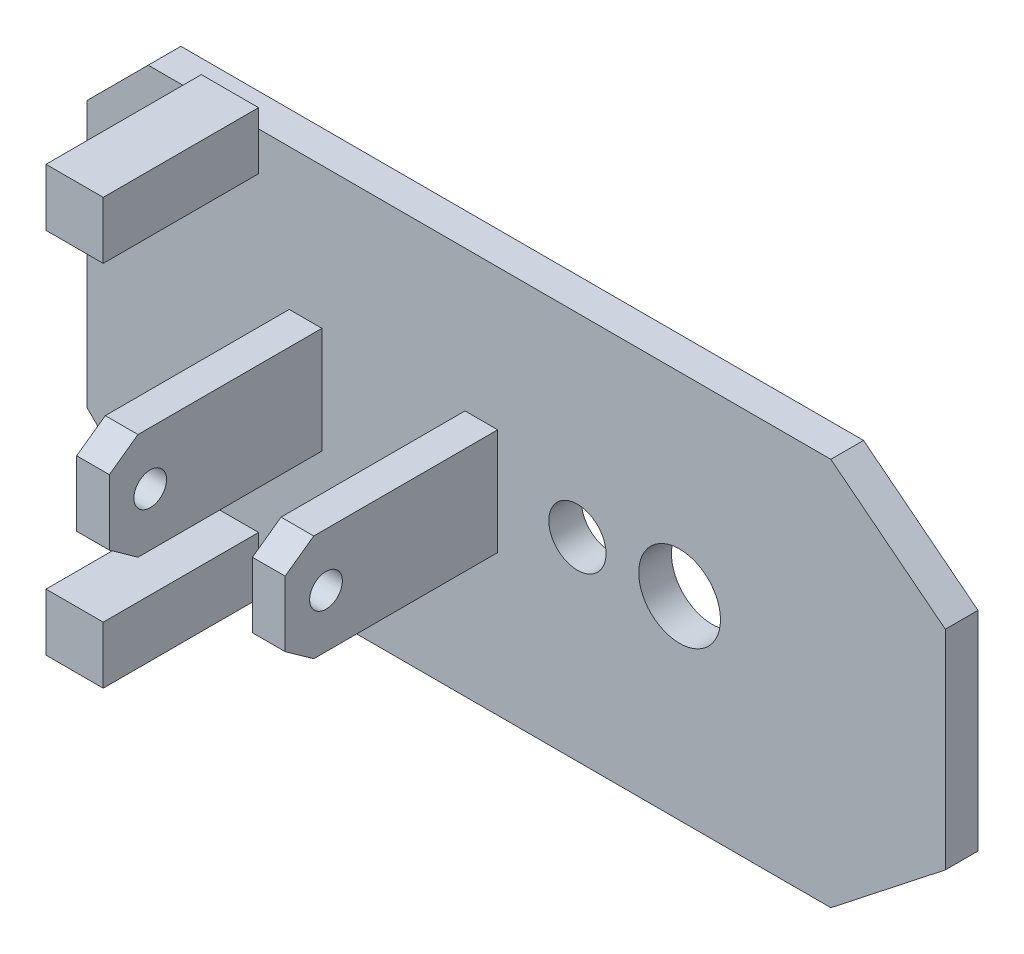
SolidWorks part; units mm, degrees
material "6061-T6 (SS)"
ref_plane "Front Plane" through (0, 0, 0) normal (0, 0, 1) x (1, 0, 0)
ref_plane "Top Plane" through (0, 0, 0) normal (0, 1, 0) x (1, 0, 0)
ref_plane "Right Plane" through (0, 0, 0) normal (1, 0, 0) x (0, 0, -1)
ref_plane "PL_Sole_Plate_base" through (0, 0, -50) normal (0, 0, 1) x (1, 0, 0)
sketch "SK_Sole_Plate" plane through (0, 0, -50) normal (0, 0, 1) x (1, 0, 0)
  line L0 (-60, -47.5) -> (107, -47.5)
  line L1 (107, -47.5) -> (135, -25.5)
  line L2 (135, -25.5) -> (135, 25.5)
  line L3 (135, 25.5) -> (107, 47.5)
  line L4 (107, 47.5) -> (-60, 47.5)
  line L5 (-60, 47.5) -> (-75, 32.5)
  line L6 (-75, 32.5) -> (-75, -32.5)
  line L7 (-75, -32.5) -> (-60, -47.5)
  circle A0 centre (70, 0) radius 10
  circle A1 centre (45, 0) radius 7
  dimension "D17_SK_Sole_Plate" = 20
  dimension "D19_SK_Sole_Plate" = 14
  dimension "P1" = 60
  dimension "P2" = 47.5
  dimension "P3" = 107
  dimension "P4" = 47.5
  dimension "P5" = 135
  dimension "P6" = 25.5
  dimension "P7" = 135
  dimension "P8" = 25.5
  dimension "P9" = 107
  dimension "P10" = 47.5
  dimension "P11" = 60
  dimension "P12" = 47.5
  dimension "P13" = 75
  dimension "P14" = 32.5
  dimension "P15" = 75
  dimension "P16" = 32.5
  dimension "P18" = 70
  dimension "P20" = 45
extrude "Sole_Plate" add sketch "SK_Sole_Plate" along normal blind 8
ref_plane "PL_Clevis_Front_base" through (17.5, 0, 0) normal (1, 0, 0) x (0, 0, -1)
sketch "SK_Clevis_Front" plane through (17.5, 0, 0) normal (1, 0, 0) x (0, 0, -1)
  line L0 (42, -13) -> (42, 13)
  line L1 (42, 13) -> (-3, 13)
  line L2 (-3, 13) -> (-10, 8)
  line L3 (-10, 8) -> (-10, -8)
  line L4 (-10, -8) -> (-3, -13)
  line L5 (-3, -13) -> (42, -13)
  circle A0 centre (0, 0) radius 4
  dimension "D13_SK_Clevis_Front" = 8
  dimension "P1" = 42
  dimension "P2" = 13
  dimension "P3" = 42
  dimension "P4" = 13
  dimension "P5" = 3
  dimension "P6" = 13
  dimension "P7" = 10
  dimension "P8" = 8
  dimension "P9" = 10
  dimension "P10" = 8
  dimension "P11" = 3
  dimension "P12" = 13
extrude "Clevis_Front" add sketch "SK_Clevis_Front" along normal blind 8
ref_plane "PL_Clevis_Back_base" through (-25.5, 0, 0) normal (1, 0, 0) x (0, 0, -1)
sketch "SK_Clevis_Back" plane through (-25.5, 0, 0) normal (1, 0, 0) x (0, 0, -1)
  line L0 (42, -13) -> (42, 13)
  line L1 (42, 13) -> (-3, 13)
  line L2 (-3, 13) -> (-10, 8)
  line L3 (-10, 8) -> (-10, -8)
  line L4 (-10, -8) -> (-3, -13)
  line L5 (-3, -13) -> (42, -13)
  circle A0 centre (0, 0) radius 4
  dimension "D13_SK_Clevis_Back" = 8
  dimension "P1" = 42
  dimension "P2" = 13
  dimension "P3" = 42
  dimension "P4" = 13
  dimension "P5" = 3
  dimension "P6" = 13
  dimension "P7" = 10
  dimension "P8" = 8
  dimension "P9" = 10
  dimension "P10" = 8
  dimension "P11" = 3
  dimension "P12" = 13
extrude "Clevis_Back" add sketch "SK_Clevis_Back" along normal blind 8
ref_plane "PL_Post_Lat_base" through (0, 0, -42) normal (0, 0, 1) x (1, 0, 0)
sketch "SK_Post_Lat" plane through (0, 0, -42) normal (0, 0, 1) x (1, 0, 0)
  line L0 (-47, 38) -> (-33, 38)
  line L1 (-33, 38) -> (-33, 52)
  line L2 (-33, 52) -> (-47, 52)
  line L3 (-47, 52) -> (-47, 38)
  dimension "P1" = 47
  dimension "P2" = 38
  dimension "P3" = 33
  dimension "P4" = 38
  dimension "P5" = 33
  dimension "P6" = 52
  dimension "P7" = 47
  dimension "P8" = 52
extrude "Post_Lat" add sketch "SK_Post_Lat" along normal blind 38
ref_plane "PL_Post_Med_base" through (0, 0, -42) normal (0, 0, 1) x (1, 0, 0)
sketch "SK_Post_Med" plane through (0, 0, -42) normal (0, 0, 1) x (1, 0, 0)
  line L0 (-47, -52) -> (-33, -52)
  line L1 (-33, -52) -> (-33, -38)
  line L2 (-33, -38) -> (-47, -38)
  line L3 (-47, -38) -> (-47, -52)
  dimension "P1" = 47
  dimension "P2" = 52
  dimension "P3" = 33
  dimension "P4" = 52
  dimension "P5" = 33
  dimension "P6" = 38
  dimension "P7" = 47
  dimension "P8" = 38
extrude "Post_Med" add sketch "SK_Post_Med" along normal blind 38
ref_axis "AX_Roll" through (-85.5, 0, 0) along (1, 0, 0)
sketch "SK_RodBalls" plane through (0, 0, 0) normal (0, 0, 1) x (1, 0, 0)
  point P0 (-40, 45)
  point P2 (-40, -45)
  dimension "P1" = 40
  dimension "P2" = 45
  dimension "P3" = 40
  dimension "P4" = 45
equation "\"Foot_length\"= 210"
equation "\"Foot_width\"= 95"
equation "\"Ankle_height\"= 50"
